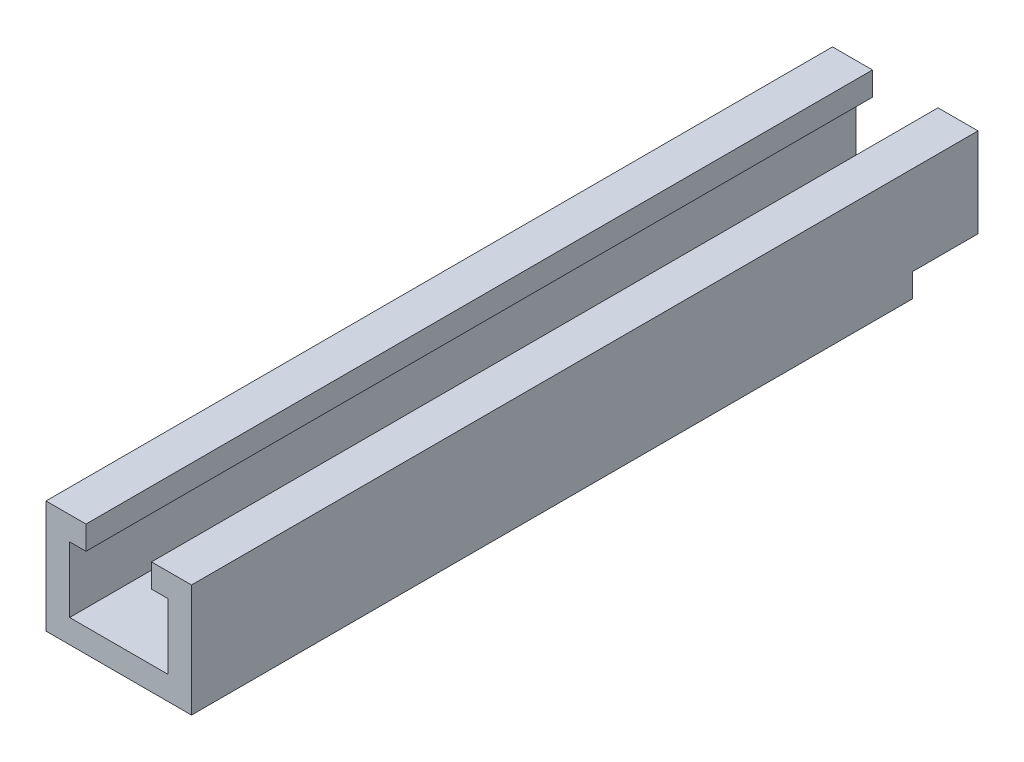
SolidWorks part; units mm, degrees
material "Beech"
ref_plane "Front Plane" through (0, 0, 0) normal (0, 0, 1) x (1, 0, 0)
ref_plane "Top Plane" through (0, 0, 0) normal (0, 1, 0) x (1, 0, 0)
ref_plane "Right Plane" through (0, 0, 0) normal (1, 0, 0) x (0, 0, -1)
sketch "Sketch1" plane through (0, 0, 0) normal (0, 0, 1) x (1, 0, 0)
  line L1 (0, 0) -> (111, 0)
  line L2 (0, 0) -> (0, 18)
  line L3 (0, 18) -> (111, 18)
  line L4 (111, 0) -> (111, 18)
  dimension "D1" = 18
  dimension "D2" = 111
extrude "baseplate" add sketch "Sketch1" along normal blind 600
sketch "Sketch2" plane through (0, 18, 0) normal (0, 1, 0) x (1, 0, 0)
  line L0 (111, -600) -> (0, -600) construction
  line L1 (0, 0) -> (18, 0)
  line L2 (0, 0) -> (0, -600)
  line L3 (0, -600) -> (18, -600)
  line L4 (18, 0) -> (18, -600)
  dimension "D1" = 18
extrude "side_rail" add sketch "Sketch2" along normal blind 50
sketch "Sketch3" plane through (0, 68, 0) normal (0, 1, 0) x (1, 0, 0)
  line L0 (111, -600) -> (18, -600) construction
  line L1 (0, 0) -> (30.5, 0)
  line L2 (0, 0) -> (0, -600)
  line L3 (0, -600) -> (30.5, -600)
  line L4 (30.5, 0) -> (30.5, -600)
  dimension "D1" = 30.5
extrude "keeper rail" add sketch "Sketch3" along normal blind 18
ref_plane "longitudinal midplane" through (55.5, 0, 0) normal (-1, 0, 0) x (0, 0, 1)
mirror "mirror rails" about plane through (55.5, 0, 0) normal (-1, 0, 0) of "keeper rail", "side_rail"
sketch "Sketch5" plane through (0, 0, 0) normal (0, -1, 0) x (1, 0, 0)
  line L0 (111, 600) -> (111, 0) construction
  line L1 (0, 0) -> (111, 0)
  line L2 (0, 0) -> (0, 50)
  line L3 (0, 50) -> (111, 50)
  line L4 (111, 0) -> (111, 50)
  dimension "D1" = 50
extrude "lap joint cutout" cut sketch "Sketch5" against normal blind 18
hole_wizard "lap joint bolt hole pattern" positions "Sketch7" profile "Sketch9" tap size "M5x0.8" standard "ANSI Metric"
sketch "Sketch7" plane through (0, 18, 0) normal (0, -1, 0) x (-1, 0, 0)
  line L1 (-102, -10) -> (-9, -10)
  line L2 (-102, -10) -> (-102, -40)
  line L3 (-102, -40) -> (-9, -40)
  line L4 (-9, -10) -> (-9, -40)
  line L5 (-102, 0) -> (-102, -10)
  line L6 (-93, 0) -> (-111, 0) construction
  line L8 (-9, -10) -> (-9, 0)
  line L9 (0, 0) -> (-18, 0) construction
  line L10 (-9, -25) -> (0, -25)
  line L11 (0, -50) -> (0, 0) construction
  point P1 (-102, -10)
  point P2 (-9, -40)
  point P113 (-102, -40)
  point P114 (-9, -10)
sketch "Sketch9" plane through (102, 18, 10) normal (1, 0, 0) x (0, 0, -1)
  line L0 (0, 0) -> (0, 15.2618)
  line L1 (0, 15.2618) -> (2.1, 14)
  line L2 (2.1, 14) -> (2.1, 0)
  line L5 (2.1, 0) -> (0, 0)
  line L10 (0, 15.2618) -> (-2.1, 14) construction
  line L11 (0, -6.35) -> (0, 107.95) construction
  dimension "Tap Drill Dia." = 4.2
  dimension "Tap Drill Depth" = 14
  dimension "Drill Angle" = 118
equation "\"board_thickness\" = 18mm"
equation "\"way_width\"= 75mm"
equation "\"way_thickness\"= 50mm"
equation "\"radial_clearance\"= 0.1mm"
equation "\"slider_width\"= \"way_width\"-2* \"radial_clearance\""
equation "\"slider_thickness\" = \"way_thickness\" - 2 * \"radial_clearance\""
equation "\"column_width\"= \"way_width\" + 2 * \"board_thickness\""
equation "\"D1@Sketch1\"=\"board_thickness\""
equation "\"D2@Sketch1\"=\"column_width\""
equation "\"D1@Sketch2\"=\"board_thickness\""
equation "\"D1@keeper rail\"=\"board_thickness\""
equation "\"boxway_slot_width\" = 50mm"
equation "\"keeper_rail_width\" = (\"column_width\" - \"boxway_slot_width\")/2"
equation "\"D1@Sketch3\"=\"keeper_rail_width\""
equation "\"slider_length\" = 125mm"
equation "\"nut_diameter\"= 22mm"
equation "\"nut_length\"= 15mm"
equation "\"leadscrew_diameter\"= 10mm"
equation "\"leadscrew_radial_clearance\"= 1mm"
equation "\"bearing_bolt_pattern_width\" = 35mm"
equation "\"bearing_bolt_pattern_height\" = 60mm"
equation "\"desktop_bolt_pattern_width\" = 30mm"
equation "\"desktop_bolt_pattern_height\" = 30mm"
equation "\"bearing_bolt_nut_counterbore_diameter\" = 12mm"
equation "\"bearing_bolt_nut_counterbore_depth\"= 10mm"
equation "\"desktop_depth\"= 500mm"
equation "\"desktop_width\"= 650mm"
equation "\"desktop_thickness\"= 18mm"
equation "\"leg_height\"=100mm"
equation "\"leg_width\"=18mm"
equation "\"leg_length\"=500mm"
equation "\"D1@lap joint cutout\" = \"leg_width\""
equation "\"lap_joint_height\" = 50mm"
equation "\"lap_dowel_diameter\"= 8mm"
equation "\"lap_dowel_hole_z_spacing\"=30"
equation "\"D1@Sketch5\"=\"lap_joint_height\""
equation "\"D1@Sketch7\"=\"lap_dowel_hole_z_spacing\""
